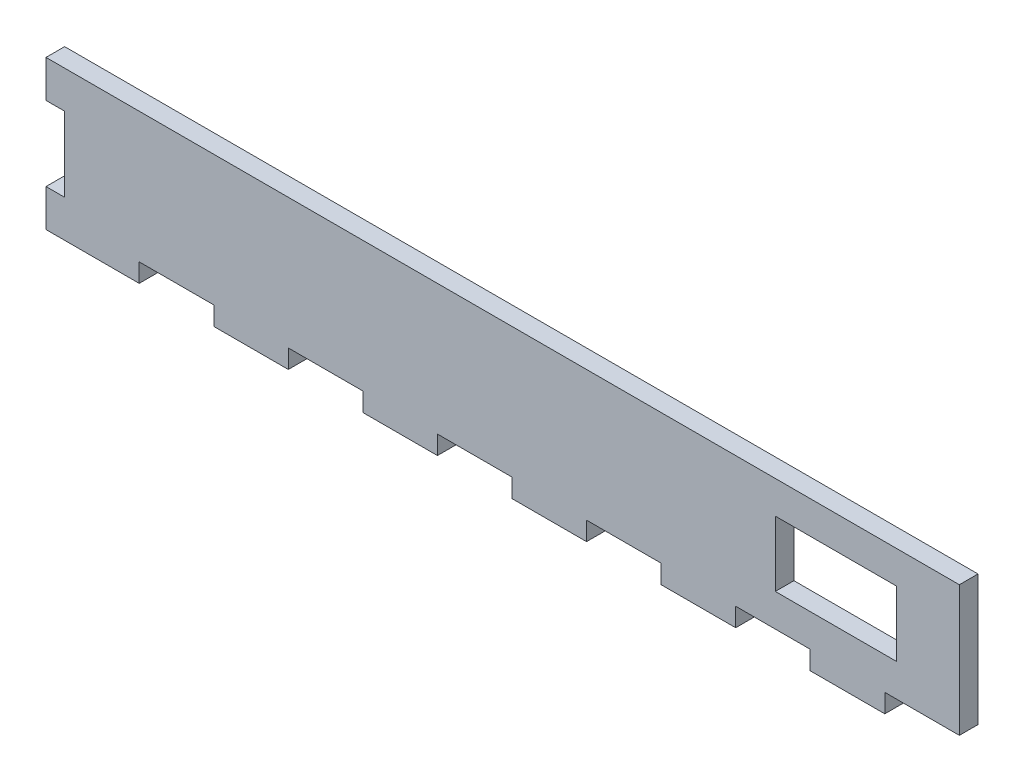
SolidWorks part; units mm, degrees
ref_plane "Front Plane" through (0, 0, 0) normal (0, 0, 1) x (1, 0, 0)
ref_plane "Top Plane" through (0, 0, 0) normal (0, 1, 0) x (1, 0, 0)
ref_plane "Right Plane" through (0, 0, 0) normal (1, 0, 0) x (0, 0, -1)
sketch "Sketch1" plane through (0, 0, 0) normal (0, 0, 1) x (1, 0, 0)
  line L0 (-262.733, -54.9538) -> (-262.733, 69.85) construction
  line L1 (42.067, 22.225) -> (-262.733, 22.225)
  line L2 (42.067, 22.225) -> (42.067, -22.225)
  line L3 (42.067, -22.225) -> (-262.733, -22.225)
  line L4 (-262.733, 22.225) -> (-262.733, -22.225)
  line L5 (63.0291, 0) -> (-62.7737, 0) construction
  line L6 (-19.6295, 10.033) -> (19.6295, 10.033) construction
  line L7 (19.6295, -10.033) -> (-19.6295, -10.033) construction
  line L8 (27.25, 6.27) -> (27.25, 8.0899) construction
  dimension "D1" = 44.45
  dimension "D2" = 14.817
extrude "Boss-Extrude1" add sketch "Sketch1" along normal blind 6.35
sketch "Sketch2" plane through (0, 0, 6.35) normal (0, 0, 1) x (1, 0, 0)
  line L0 (-41.9443, 0) -> (30.2812, 0) construction
  line L1 (-20.6375, 11.1125) -> (20.6375, 11.1125)
  line L2 (-20.6375, 11.1125) -> (-20.6375, -11.1125)
  line L3 (-20.6375, -11.1125) -> (20.6375, -11.1125)
  line L4 (20.6375, 11.1125) -> (20.6375, -11.1125)
  line L5 (-19.6295, 10.033) -> (19.6295, 10.033) construction
  line L6 (19.6295, -10.033) -> (-19.6295, -10.033) construction
  line L7 (0, 34.6052) -> (0, -28.4279) construction
  line L8 (-20.1295, -9.533) -> (-20.1295, 9.533) construction
  line L9 (20.1295, 9.533) -> (20.1295, -9.533) construction
  dimension "D1" = 22.225
  dimension "D2" = 41.275
extrude "Cut-Extrude1" cut sketch "Sketch2" against normal through all
ref_plane "Plane1" through (42.067, -22.225, 6.35) normal (1, 0, 0) x (0, 0, -1)
sketch "Sketch5" plane through (0, -22.225, 0) normal (0, -1, 0) x (1, 0, 0)
  line L0 (-262.733, 6.35) -> (42.067, 6.35) construction
  line L1 (16.667, 6.35) -> (-8.733, 6.35)
  line L2 (16.667, 6.35) -> (16.667, 0)
  line L3 (16.667, 0) -> (-8.733, 0)
  line L4 (-8.733, 6.35) -> (-8.733, 0)
  line L5 (-262.733, 0) -> (42.067, 0) construction
  dimension "D1" = 25.4
  dimension "D2" = 25.4
extrude "Boss-Extrude2" add sketch "Sketch5" along normal blind 6.35
pattern_linear "LPattern1" count 6 spacing 50.8 along (-1, 0, 0) of "Boss-Extrude2"
sketch "Sketch6" plane through (-262.733, 0, 0) normal (-1, 0, 0) x (0, 0, 1)
  line L0 (0, 22.225) -> (6.35, 22.225)
  line L1 (6.35, 22.225) -> (6.35, 9.525)
  line L2 (6.35, 22.225) -> (6.35, -28.575) construction
  line L3 (6.35, 9.525) -> (0, 9.525)
  line L4 (0, 22.225) -> (0, -28.575) construction
  line L5 (0, 9.525) -> (0, 22.225)
  dimension "D1" = 12.7
extrude "Boss-Extrude3" add sketch "Sketch6" along normal blind 6.35
pattern_linear "LPattern2" count 2 spacing 38.1 along (0, -1, 0) of "Boss-Extrude3"
